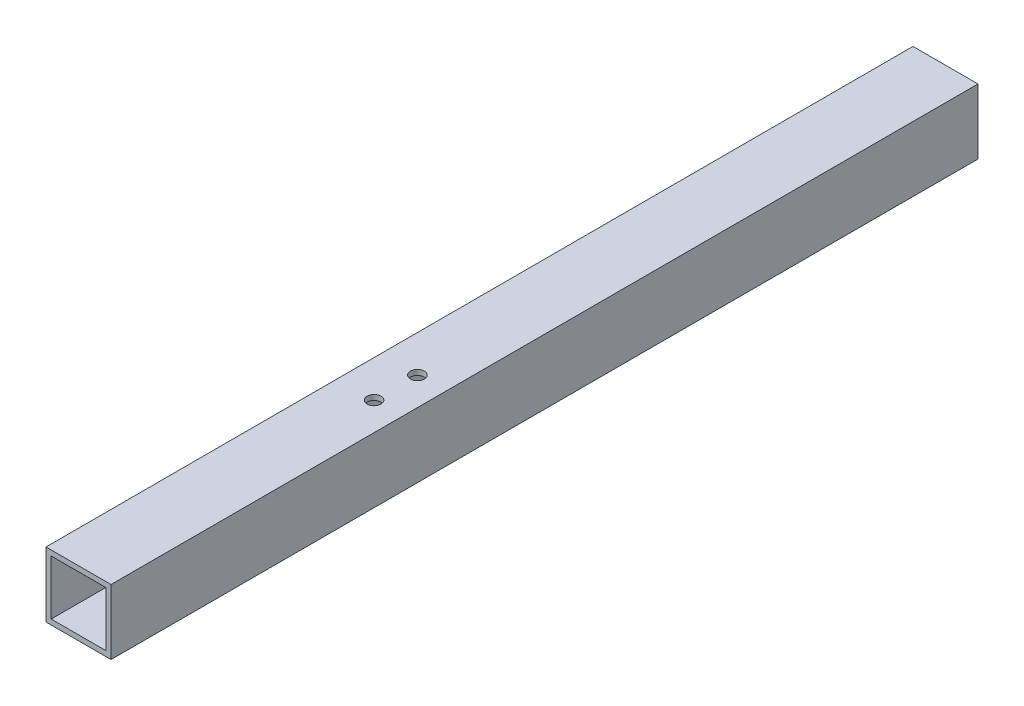
SolidWorks part; units mm, degrees
material "7050-T73510"
ref_plane "Front" through (0, 0, 0) normal (0, 0, 1) x (1, 0, 0)
ref_plane "Top" through (0, 0, 0) normal (0, 1, 0) x (1, 0, 0)
ref_plane "Right" through (0, 0, 0) normal (1, 0, 0) x (0, 0, -1)
sketch "草图1" plane through (0, 0, 0) normal (0, 0, 1) x (1, 0, 0)
  line L0 (-6.3, -6.3) -> (-6.3, 6.3)
  line L1 (-7.5, -7.5) -> (7.5, -7.5)
  line L2 (-7.5, -7.5) -> (-7.5, 7.5)
  line L3 (-7.5, 7.5) -> (7.5, 7.5)
  line L4 (7.5, -7.5) -> (7.5, 7.5)
  line L5 (-7.5, -7.5) -> (7.5, 7.5) construction
  line L6 (-7.5, 7.5) -> (7.5, -7.5) construction
  line L7 (-6.3, 6.3) -> (6.3, 6.3)
  line L8 (6.3, -6.3) -> (6.3, 6.3)
  line L9 (-6.3, -6.3) -> (6.3, -6.3)
  point P0 (0, 0)
  dimension "D1" = 15
  dimension "D2" = 15
  dimension "D3" = 1.2
extrude "凸台-拉伸1" add sketch "草图1" along normal blind 200
sketch "草图2" plane through (0, -7.5, 0) normal (0, -1, 0) x (1, 0, 0)
  circle A2 centre (1, 132.8224) radius 1.6
  circle A3 centre (1, 122.8224) radius 1.6
extrude "切除-拉伸1" cut sketch "草图2" against normal blind 25
